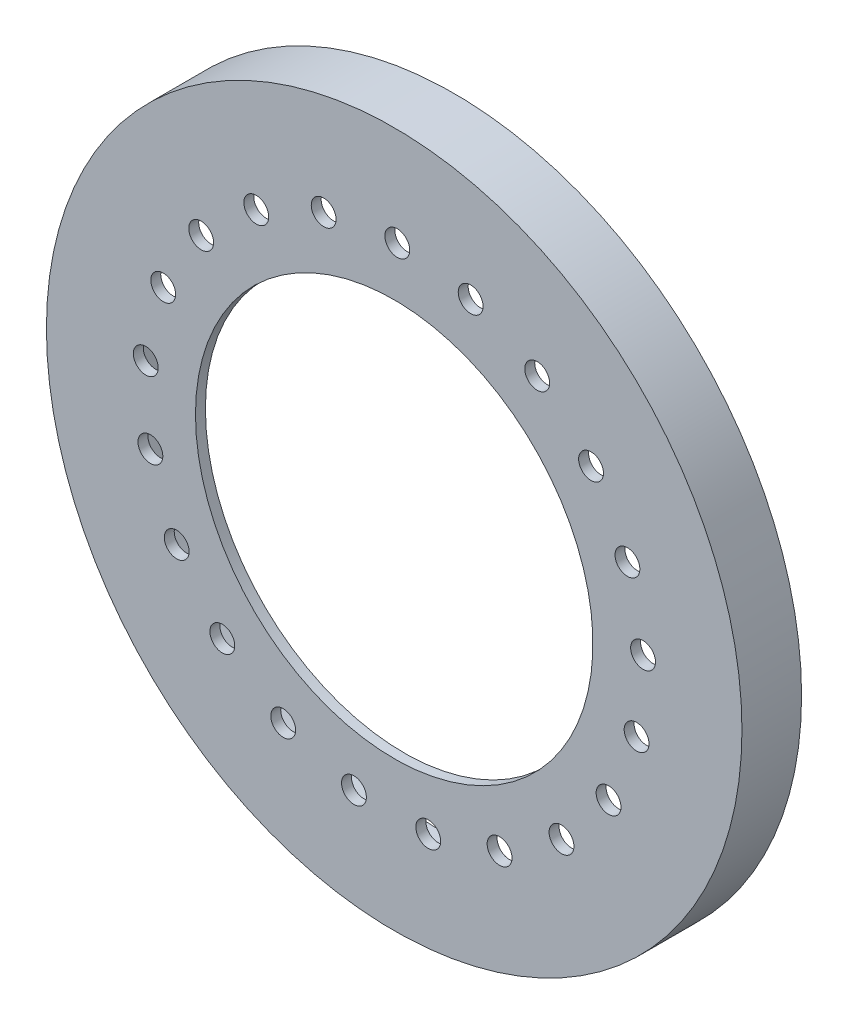
SolidWorks part; units mm, degrees
ref_plane "Front Plane" through (0, 0, 0) normal (0, 0, 1) x (1, 0, 0)
ref_plane "Top Plane" through (0, 0, 0) normal (0, 1, 0) x (1, 0, 0)
ref_plane "Right Plane" through (0, 0, 0) normal (1, 0, 0) x (0, 0, -1)
sketch "Sketch1" plane through (0, 0, 0) normal (0, 0, 1) x (1, 0, 0)
  circle A1 centre (0, 0) radius 76.2
  circle A2 centre (0, 0) radius 50.8
  point P50 (0, 0)
  dimension "D2" = 152.4
  dimension "D3" = 25.4
sketch "Sketch3" plane through (0, 0, 0) normal (0, 0, 1) x (1, 0, 0)
  circle A0 centre (0, 0) radius 88.9
  dimension "D1" = 177.8
extrude "Boss-Extrude2" add sketch "Sketch3" along normal blind 15.24
extrude "Cut-Extrude1" cut sketch "Sketch1" along normal blind 12.7
sketch "Sketch4" plane through (0, 0, 0) normal (0, 0, 1) x (1, 0, 0)
  circle A0 centre (-63.5, 5.5537) radius 3.175
  circle A1 centre (-59.0419, 24.0239) radius 3.175
  circle A2 centre (-49.3376, 40.3595) radius 3.175
  circle A3 centre (-35.2495, 53.109) radius 3.175
  circle A4 centre (-18.0293, 61.1395) radius 3.175
  circle A5 centre (0.7928, 63.7375) radius 3.175
  circle A6 centre (19.5446, 60.6721) radius 3.175
  circle A7 centre (36.5597, 52.2158) radius 3.175
  circle A8 centre (50.3263, 39.1198) radius 3.175
  circle A9 centre (59.6212, 22.5479) radius 3.175
  circle A10 centre (63.6185, 3.9725) radius 3.175
  circle A11 centre (61.963, -14.9559) radius 3.175
  circle A12 centre (54.8019, -32.5553) radius 3.175
  circle A13 centre (42.7713, -47.2621) radius 3.175
  circle A14 centre (26.9403, -57.7695) radius 3.175
  circle A15 centre (8.7156, -63.1437) radius 3.175
  circle A16 centre (-10.2835, -62.9074) radius 3.175
  circle A17 centre (-28.369, -57.0815) radius 3.175
  circle A18 centre (-43.9337, -46.1836) radius 3.175
  circle A19 centre (-55.5947, -31.1821) radius 3.175
  circle A20 centre (-62.3159, -13.41) radius 3.175
  circle A21 centre (0, 0) radius 50.8
  point P45 (0, 0)
  dimension "D1" = 6.35
  dimension "D2" = 63.5
  dimension "D3" = 21
extrude "Cut-Extrude3" cut sketch "Sketch4" along normal through all
